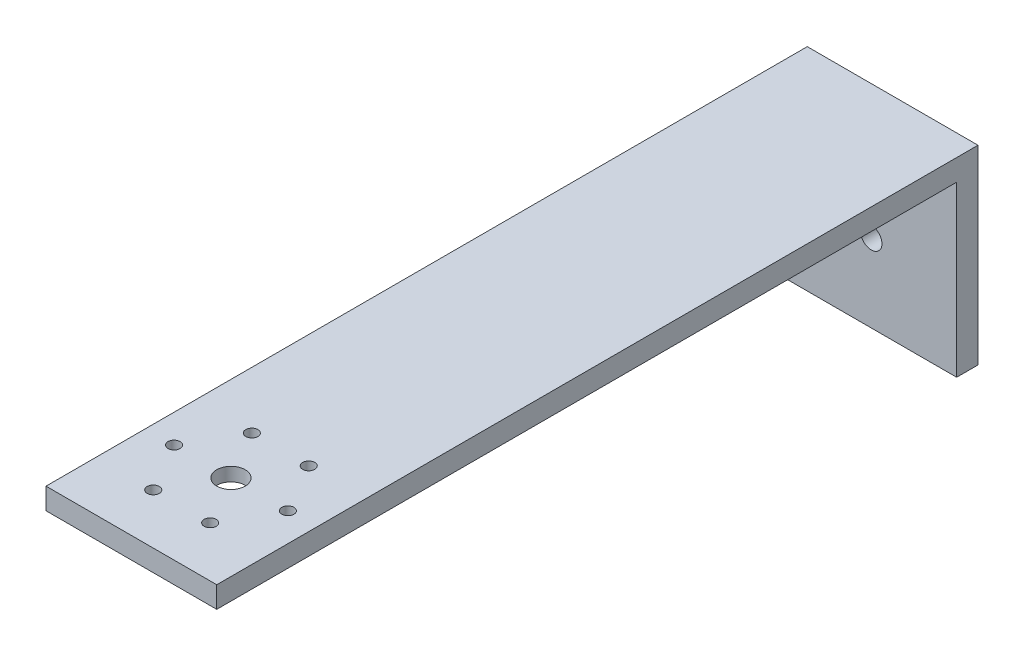
SolidWorks part; units mm, degrees
material "6061-T6 (SS)"
ref_plane "Front Plane" through (0, 0, 0) normal (0, 0, 1) x (1, 0, 0)
ref_plane "Top Plane" through (0, 0, 0) normal (0, 1, 0) x (1, 0, 0)
ref_plane "Right Plane" through (0, 0, 0) normal (1, 0, 0) x (0, 0, -1)
ref_plane "PL_Forearm_Plate_base" through (0, 25.5, 0) normal (0, 1, 0) x (1, 0, 0)
sketch "SK_Forearm_Plate" plane through (0, 25.5, 0) normal (0, 1, 0) x (1, 0, 0)
  line L0 (-24, -28) -> (24, -28)
  line L1 (24, -28) -> (24, 180)
  line L2 (24, 180) -> (-24, 180)
  line L3 (-24, 180) -> (-24, -28)
  circle A0 centre (16, 0) radius 1.7
  circle A1 centre (8, 13.8564) radius 1.7
  circle A2 centre (-8, 13.8564) radius 1.7
  circle A3 centre (-16, 0) radius 1.7
  circle A4 centre (-8, -13.8564) radius 1.7
  circle A5 centre (8, -13.8564) radius 1.7
  circle A6 centre (0, 0) radius 4
  dimension "D9_SK_Forearm_Plate" = 3.4
  dimension "D11_SK_Forearm_Plate" = 3.4
  dimension "D14_SK_Forearm_Plate" = 3.4
  dimension "D17_SK_Forearm_Plate" = 3.4
  dimension "D19_SK_Forearm_Plate" = 3.4
  dimension "D22_SK_Forearm_Plate" = 3.4
  dimension "D25_SK_Forearm_Plate" = 8
  dimension "P1" = 24
  dimension "P2" = 28
  dimension "P3" = 24
  dimension "P4" = 28
  dimension "P5" = 24
  dimension "P6" = 180
  dimension "P7" = 24
  dimension "P8" = 180
  dimension "P10" = 16
  dimension "P12" = 8
  dimension "P13" = 13.8564
  dimension "P15" = 8
  dimension "P16" = 13.8564
  dimension "P18" = 16
  dimension "P20" = 8
  dimension "P21" = 13.8564
  dimension "P23" = 8
  dimension "P24" = 13.8564
extrude "Forearm_Plate" add sketch "SK_Forearm_Plate" along normal blind 6
ref_plane "PL_Elbow_Pilot_Recess_base" through (0, 25.5, 0) normal (0, 1, 0) x (1, 0, 0)
sketch "SK_Elbow_Pilot_Recess" plane through (0, 25.5, 0) normal (0, 1, 0) x (1, 0, 0)
  circle A0 centre (0, 0) radius 12.15
  dimension "D1_SK_Elbow_Pilot_Recess" = 24.3
extrude "Elbow_Pilot_Recess" cut sketch "SK_Elbow_Pilot_Recess" along normal blind 2.2
ref_plane "PL_Hand_Plate_base" through (0, 0, -186) normal (0, 0, 1) x (1, 0, 0)
sketch "SK_Hand_Plate" plane through (0, 0, -186) normal (0, 0, 1) x (1, 0, 0)
  line L0 (-24, -22) -> (24, -22)
  line L1 (24, -22) -> (24, 31.5)
  line L2 (24, 31.5) -> (-24, 31.5)
  line L3 (-24, 31.5) -> (-24, -22)
  circle A0 centre (0, 0) radius 3
  dimension "D9_SK_Hand_Plate" = 6
  dimension "P1" = 24
  dimension "P2" = 22
  dimension "P3" = 24
  dimension "P4" = 22
  dimension "P5" = 24
  dimension "P6" = 31.5
  dimension "P7" = 24
  dimension "P8" = 31.5
extrude "Hand_Plate" add sketch "SK_Hand_Plate" along normal blind 6
equation "\"Forearm_length\"= 180"
